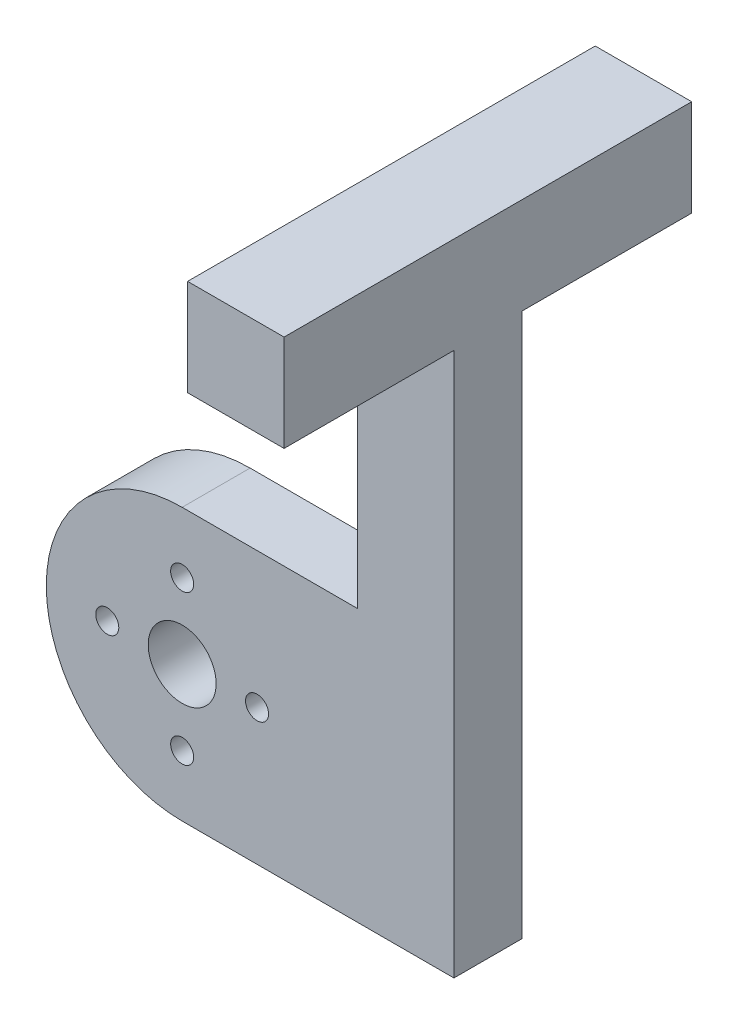
SolidWorks part; units mm, degrees
ref_plane "Front Plane" through (0, 0, 0) normal (0, 0, 1) x (1, 0, 0)
ref_plane "Top Plane" through (0, 0, 0) normal (0, 1, 0) x (1, 0, 0)
ref_plane "Right Plane" through (0, 0, 0) normal (1, 0, 0) x (0, 0, -1)
sketch "Sketch2" plane through (0, 0, 0) normal (0, 0, 1) x (1, 0, 0)
  line L0 (16.383, 47.117) -> (25.4, 47.117)
  line L1 (16.383, 47.117) -> (16.383, 12.7)
  line L2 (16.383, 12.7) -> (0, 12.7)
  line L3 (25.4, 47.117) -> (25.4, -12.7)
  line L4 (25.4, -12.7) -> (0, -12.7)
  circle A0 centre (0, 0) radius 12.7
  circle A1 centre (7, 0) radius 1.077
  circle A2 centre (0, -7) radius 1.077
  circle A3 centre (-7, 0) radius 1.077
  circle A4 centre (0, 7) radius 1.077
  point P14 (0, 0)
  dimension "D1" = 25.4
  dimension "D3" = 2.154
  dimension "D2" = 7
  dimension "D5" = 47.117
  dimension "D6" = 16.383
  dimension "D7" = 25.4
  dimension "D8" = 9.017
  dimension "D4" = 4
extrude "Boss-Extrude1" add sketch "Sketch2" along normal mid plane 6.35 contours A0 L4 L3 L0 L1 L2 | A0 A4 A3 A2 A1 region at (18.9582, 13.2191, 0) region at (0, 0, 0)
sketch "Sketch3" plane through (0, 0, 0) normal (0, 0, -1) x (-1, 0, 0)
  line L0 (-16.383, 47.117) -> (-16.383, 12.7) construction
  line L1 (-25.4, 47.117) -> (-16.383, 47.117)
  line L2 (-25.4, 47.117) -> (-25.4, 38.1)
  line L3 (-25.4, 38.1) -> (-16.383, 38.1)
  line L4 (-16.383, 47.117) -> (-16.383, 38.1)
extrude "Boss-Extrude2" add sketch "Sketch3" along normal mid plane 38.1
sketch "Sketch4" plane through (0, 0, 3.175) normal (0, 0, 1) x (1, 0, 0)
  circle A0 centre (0, 0) radius 3.175
  dimension "D1" = 6.35
extrude "Cut-Extrude1" cut sketch "Sketch4" against normal through all
equation "\"D2@Sketch2\"=7mm"
equation "\"tightTol\"= 0.005in"
equation "\"normTol\"= 0.01in"
equation "\"looseTol\"= 0.02in"
equation "\"D3@Sketch2\"=1.9mm+\"normTol\""
equation "\"D6@Sketch2\"=0.625+\"looseTol\""
equation "\"D5@Sketch2\"=1.875-\"looseTol\""
